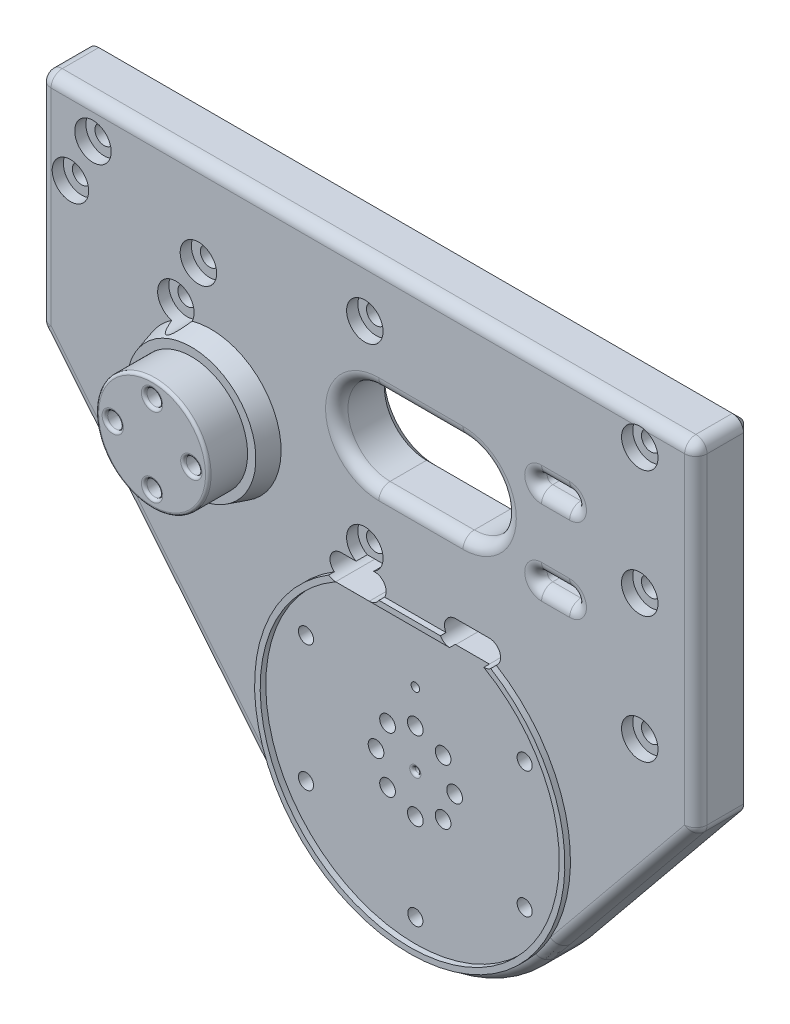
SolidWorks part; units mm, degrees
ref_plane "Front Plane" through (0, 0, 0) normal (0, 0, 1) x (1, 0, 0)
ref_plane "Top Plane" through (0, 0, 0) normal (0, 1, 0) x (1, 0, 0)
ref_plane "Right Plane" through (0, 0, 0) normal (1, 0, 0) x (0, 0, -1)
sketch "Sketch1" plane through (0, 0, 0) normal (0, 0, 1) x (1, 0, 0)
  line L0 (-36.42, 37.54) -> (-36.42, 0) construction
  line L1 (-66.92, 75) -> (50, 75)
  line L2 (-66.92, 75) -> (-66.92, -30)
  line L3 (-66.92, -30) -> (50, -30)
  line L4 (50, 75) -> (50, -30)
  line L5 (-36.42, 0) -> (0, 0) construction
  circle A0 centre (0, 0) radius 0.5
  circle A1 centre (-36.42, 37.54) radius 0.5
  dimension "D1" = 1
  dimension "D2" = 1
  dimension "D3" = 36.42
  dimension "D4" = 37.54
  dimension "D5" = 50
  dimension "D6" = 30
  dimension "D7" = 30
  dimension "D8" = 37.46
extrude "Boss-Extrude1" add sketch "Sketch1" along normal blind 10
ref_axis "Axis1" through (-36.42, 37.54, 10) along (0, 0, -1)
ref_plane "Plane1" through (0, 37.54, 0) normal (0, 1, 0) x (0, 0, -1)
sketch "Sketch5" plane through (0, 37.54, 0) normal (0, 1, 0) x (0, 0, -1)
  line L0 (-10, 36.92) -> (-10, 35.92) construction
  line L1 (-10, 36.92) -> (-10, 35.92) construction
  line L2 (-10, 36.42) -> (-20.5, 36.42) construction
  line L3 (-20.5, 36.42) -> (-20.5, 26.395)
  line L4 (-20.5, 26.395) -> (-13.5, 26.395)
  line L5 (-13.5, 26.395) -> (-13.5, 24.92)
  line L6 (-13.5, 24.92) -> (-10, 23.92)
  line L7 (-10, 66.92) -> (-10, -50) construction
  line L8 (-10, 36.42) -> (-10, 23.92)
  line L9 (-10, 36.42) -> (-20.5, 36.42)
  line L11 (-13.5, 108.28) -> (-13.5, 138.68) construction
  dimension "D1" = 23
  dimension "D2" = 20.05
  dimension "D3" = 7
  dimension "D4" = 12.5
  dimension "D5" = 3.5
revolve "Revolve1" add sketch "Sketch5" angle 360 about L9
sketch "Sketch6" plane through (0, 0, 20.5) normal (0, 0, 1) x (1, 0, 0)
  line L0 (-36.42, 37.54) -> (-36.42, 44.54) construction
  circle A0 centre (-36.42, 44.54) radius 1.4
  circle A1 centre (-29.42, 37.54) radius 1.4
  circle A2 centre (-36.42, 30.54) radius 1.4
  circle A3 centre (-43.42, 37.54) radius 1.4
  point P13 (-36.42, 37.54)
  dimension "D1" = 7
  dimension "D2" = 2.8
  dimension "D3" = 4
extrude "Cut-Extrude1" cut sketch "Sketch6" against normal through all
sketch "Sketch10" plane through (0, 0, 0) normal (0, 0, -1) x (-1, 0, 0)
  circle A0 centre (0, 0) radius 22.5 construction
  circle A1 centre (-19.484, 11.2528) radius 1.35
  arc A7 (-19.4838, 12.2778) -> (-19.4841, 10.2278) centre (-19.484, 11.2528) ccw construction
  arc A8 (-19.4838, 12.2778) -> (-19.4841, 10.2278) centre (-19.484, 11.2528) ccw construction
  arc A9 (19.4873, 12.2722) -> (19.487, 10.2222) centre (19.4872, 11.2472) ccw construction
  arc A10 (19.4841, -10.2278) -> (19.4838, -12.2778) centre (19.484, -11.2528) ccw construction
  arc A11 (-0.0031, -21.475) -> (-0.0033, -23.525) centre (-0.0032, -22.5) ccw construction
  arc A12 (-19.487, -10.2222) -> (-19.4873, -12.2722) centre (-19.4872, -11.2472) ccw construction
  arc A13 (19.4873, 12.2722) -> (19.487, 10.2222) centre (19.4872, 11.2472) ccw construction
  arc A14 (19.4841, -10.2278) -> (19.4838, -12.2778) centre (19.484, -11.2528) ccw construction
  arc A15 (-0.0031, -21.475) -> (-0.0033, -23.525) centre (-0.0032, -22.5) ccw construction
  arc A16 (-19.487, -10.2222) -> (-19.4873, -12.2722) centre (-19.4872, -11.2472) ccw construction
  circle A17 centre (-19.4872, -11.2472) radius 1.35
  circle A18 centre (-0.0032, -22.5) radius 1.35
  circle A19 centre (19.484, -11.2528) radius 1.35
  circle A20 centre (19.4872, 11.2472) radius 1.35
  point P17 (0, 0)
  dimension "D1" = 45
  dimension "D2" = 2.7
extrude "Ak45 holes" cut sketch "Sketch10" against normal through all
fillet "Fillet3" radius 0.5 6 edges at (-46.445, 37.54, 20.5) (-42.02, 37.54, 20.5) (-35.02, 30.54, 20.5) (-28.02, 37.54, 20.5) (-35.02, 44.54, 20.5) (0.5, 0, 10)
hole_wizard "CBORE for M5 Hex Head Bolt1" positions "3DSketch1" profile "Sketch14" counterbore size "M5" standard "ANSI Metric" end condition through all
sketch3d "3DSketch1"
  line L4 (19.484, 11.2528, 10) -> (19.484, 11.2528, 0) construction
  line L5 (19.4872, -11.2472, 10) -> (19.4872, -11.2472, 0) construction
  line L6 (0.0032, -22.5, 10) -> (0.0032, -22.5, 0) construction
  line L7 (-19.484, -11.2528, 10) -> (-19.484, -11.2528, 0) construction
  line L8 (-19.4872, 11.2472, 10) -> (-19.4872, 11.2472, 0) construction
  point P16 (19.484, 11.2528, 0)
  point P30 (19.4872, -11.2472, 0)
  point P34 (0.0032, -22.5, 0)
  point P38 (-19.484, -11.2528, 0)
  point P42 (-19.4872, 11.2472, 0)
sketch "Sketch14" plane through (19.484, 11.2528, 0) normal (1, 0, 0) x (0, 1, 0)
  line L0 (0, 0) -> (0, 20.5)
  line L1 (0, 20.5) -> (1.35, 20.5)
  line L3 (1.35, 20.5) -> (1.35, 2.5)
  line L4 (1.35, 2.5) -> (2.75, 2.5)
  line L5 (2.75, 2.5) -> (2.75, 0)
  line L7 (2.75, 0) -> (0, 0)
  line L11 (0, -6.35) -> (0, 107.95) construction
  dimension "Thru Hole Dia." = 2.7
  dimension "Thru Hole Depth" = 20.5
  dimension "C'Bore Dia." = 5.5
  dimension "C'Bore Depth" = 2.5
sketch "Sketch16" plane through (0, 0, 10) normal (0, 0, 1) x (1, 0, 0)
  line L0 (13.199, 23.1519) -> (-13.2056, 23.1481)
  line L1 (-12.1276, 22.9983) -> (12.1211, 23.0017) construction
  line L3 (13.4613, 24.1519) -> (-13.4682, 24.1481)
  arc A0 (-13.2056, 23.1481) -> (13.199, 23.1519) centre (0, 0) ccw
  arc A2 (0.0038, -26.5) -> (13.1592, 23.0019) centre (0, 0) ccw construction
  arc A3 (0.0038, -26.5) -> (13.1592, 23.0019) centre (0, 0) ccw construction
  arc A4 (-13.4682, 24.1481) -> (13.4613, 24.1519) centre (0, 0) ccw
  dimension "D2" = 26.5
  dimension "D3" = 26.65
  dimension "D1" = 0.15
  dimension "D4" = 1
extrude "Boss-Extrude4" add sketch "Sketch16" along normal blind 1
sketch "Sketch17" plane through (0, 0, 10) normal (0, 0, 1) x (1, 0, 0)
  line L0 (0, 7) -> (0, 0) construction
  circle A0 centre (0, 7) radius 1.4
  circle A1 centre (4.9497, 4.9497) radius 1.4
  circle A2 centre (7, 0) radius 1.4
  circle A3 centre (4.9497, -4.9497) radius 1.4
  circle A4 centre (0, -7) radius 1.4
  circle A5 centre (-4.9497, -4.9497) radius 1.4
  circle A6 centre (-7, 0) radius 1.4
  circle A7 centre (-4.9497, 4.9497) radius 1.4
  point P13 (0, 0)
  dimension "D1" = 2.8
  dimension "D2" = 7
  dimension "D3" = 8
extrude "Cut-Extrude5" cut sketch "Sketch17" against normal through all
sketch "WheelPointTravel" plane through (0, 0, 10) normal (0, 0, 1) x (1, 0, 0)
  line L0 (-67.04, -61.85) -> (-67.04, -341.8) construction
  line L1 (-57.865, -61.85) -> (-76.215, -61.85)
  line L2 (-57.865, -61.85) -> (-57.865, -341.8)
  line L3 (-57.865, -341.8) -> (-76.215, -341.8)
  line L4 (-76.215, -61.85) -> (-76.215, -341.8)
  dimension "D1" = 67.04
  dimension "D2" = 18.35
  dimension "D3" = 61.85
  dimension "D4" = 279.95
sketch "Angle Retracted Extended" plane through (0, 0, 0) normal (0, 0, -1) x (-1, 0, 0)
  line L0 (0, 0) -> (316.0647, 168.0546) construction
  line L1 (138.3785, -213.0843) -> (0, 0) construction
  line L2 (0, 0) -> (228.0086, 0) construction
  dimension "D1" = 28
  dimension "D2" = 57
sketch "Sketch18" plane through (0, 0, 10) normal (0, 0, 1) x (1, 0, 0)
  circle A0 centre (-57.4513, 68.5011) radius 1.6 construction
  circle A1 centre (-38.6577, 59.131) radius 1.6 construction
  circle A2 centre (-42.6735, 51.0766) radius 1.65 construction
  circle A3 centre (-61.4671, 60.4467) radius 1.65 construction
  circle A4 centre (-42.6735, 51.0766) radius 1.65
  circle A5 centre (-61.4671, 60.4467) radius 1.65
  circle A7 centre (-57.4513, 68.5011) radius 1.6
  circle A8 centre (-38.6577, 59.131) radius 1.6
  circle A14 centre (40, 70) radius 1.7 construction
  circle A15 centre (40, 47.5) radius 1.7 construction
  circle A16 centre (40, 25) radius 1.7 construction
  circle A17 centre (-9, 30) radius 1.7 construction
  circle A18 centre (-9, 65) radius 1.7 construction
  circle A19 centre (40, 70) radius 1.7
  circle A20 centre (40, 47.5) radius 1.7
  circle A21 centre (40, 25) radius 1.7
  circle A22 centre (-9, 30) radius 1.7
  circle A23 centre (-9, 65) radius 1.7
extrude "Fastener holes" cut sketch "Sketch18" against normal through all
hole_wizard "CBORE for M5 Hex Head Bolt2" positions "3DSketch2" profile "Sketch19" counterbore size "M5" standard "ANSI Metric" end condition through all
sketch3d "3DSketch2"
  line L0 (-57.4513, 68.5011, 0) -> (-57.4513, 68.5011, 10) construction
  line L6 (-38.6577, 59.131, 0) -> (-38.6577, 59.131, 10) construction
  line L7 (-9, 65, 0) -> (-9, 65, 10) construction
  line L8 (-9, 30, 0) -> (-9, 30, 10) construction
  line L9 (40, 25, 0) -> (40, 25, 10) construction
  line L10 (40, 47.5, 0) -> (40, 47.5, 10) construction
  line L11 (40, 70, 0) -> (40, 70, 10) construction
  line L12 (-61.4671, 60.4467, 0) -> (-61.4671, 60.4467, 10) construction
  line L13 (-61.4671, 60.4467, 0) -> (-61.4671, 60.4467, 10) construction
  line L14 (-42.6735, 51.0766, 0) -> (-42.6735, 51.0766, 10) construction
  point P0 (-57.4513, 68.5011, 10)
  point P29 (-38.6577, 59.131, 10)
  point P36 (-9, 65, 10)
  point P40 (-9, 30, 10)
  point P44 (40, 25, 10)
  point P48 (40, 47.5, 10)
  point P52 (40, 70, 10)
  point P57 (-61.4671, 60.4467, 10)
  point P61 (-61.4671, 60.4467, 10)
  point P65 (-42.6735, 51.0766, 10)
sketch "Sketch19" plane through (-57.4513, 68.5011, 10) normal (1, 0, 0) x (0, -1, 0)
  line L0 (0, 0) -> (0, 10)
  line L1 (0, 10) -> (1.65, 10)
  line L3 (1.65, 10) -> (1.65, 2)
  line L4 (1.65, 2) -> (3.25, 2)
  line L5 (3.25, 2) -> (3.25, 0)
  line L7 (3.25, 0) -> (0, 0)
  line L11 (0, -6.35) -> (0, 107.95) construction
  dimension "Thru Hole Dia." = 3.3
  dimension "Thru Hole Depth" = 10
  dimension "C'Bore Dia." = 6.5
  dimension "C'Bore Depth" = 2
sketch "Sketch20" plane through (0, 0, 0) normal (0, 0, -1) x (-1, 0, 0)
  line L0 (-50, 15) -> (-22.6599, -18.4957)
  line L1 (-50, -30) -> (-50, 75) construction
  line L2 (22.6352, -18.5259) -> (66.92, 35.582)
  line L3 (0, 0) -> (316.0647, 168.0546) construction
  line L4 (66.92, 75) -> (66.92, -30) construction
  line L5 (-50, 15) -> (-50, -30)
  line L6 (-50, -30) -> (66.92, -30)
  line L7 (66.92, -30) -> (66.92, 35.582)
  arc A0 (-22.6599, -18.4957) -> (22.6352, -18.5259) centre (0, 0) ccw
  circle A1 centre (-40, 25) radius 1.7 construction
  dimension "D1" = 58.5
  dimension "D2" = 10
extrude "Cut-Extrude7" cut sketch "Sketch20" against normal through all
sketch "Sketch21" plane through (0, 0, 0) normal (0, 0, -1) x (-1, 0, 0)
  line L0 (6.5, 40.5) -> (-8.5, 40.5) construction
  line L1 (-8.5, 55.5) -> (6.5, 55.5) construction
  line L2 (6.5, 40.5) -> (-8.5, 40.5)
  line L3 (-8.5, 55.5) -> (6.5, 55.5)
  line L4 (-22.5, 39.5) -> (-27.5, 39.5) construction
  line L5 (-27.5, 41.5) -> (-22.5, 41.5) construction
  line L6 (-22.5, 54.5) -> (-27.5, 54.5) construction
  line L7 (-27.5, 56.5) -> (-22.5, 56.5) construction
  line L8 (-22.5, 39.5) -> (-27.5, 39.5)
  line L9 (-27.5, 41.5) -> (-22.5, 41.5)
  line L10 (-22.5, 54.5) -> (-27.5, 54.5)
  line L11 (-27.5, 56.5) -> (-22.5, 56.5)
  arc A0 (6.5, 40.5) -> (6.5, 55.5) centre (6.5, 48) ccw construction
  arc A1 (-8.5, 55.5) -> (-8.5, 40.5) centre (-8.5, 48) ccw construction
  arc A2 (6.5, 40.5) -> (6.5, 55.5) centre (6.5, 48) ccw
  arc A3 (-8.5, 55.5) -> (-8.5, 40.5) centre (-8.5, 48) ccw
  arc A4 (-22.5, 39.5) -> (-22.5, 41.5) centre (-22.5, 40.5) ccw construction
  arc A5 (-27.5, 41.5) -> (-27.5, 39.5) centre (-27.5, 40.5) ccw construction
  arc A6 (-22.5, 54.5) -> (-22.5, 56.5) centre (-22.5, 55.5) ccw construction
  arc A7 (-27.5, 56.5) -> (-27.5, 54.5) centre (-27.5, 55.5) ccw construction
  arc A8 (-22.5, 39.5) -> (-22.5, 41.5) centre (-22.5, 40.5) ccw
  arc A9 (-27.5, 41.5) -> (-27.5, 39.5) centre (-27.5, 40.5) ccw
  arc A10 (-22.5, 54.5) -> (-22.5, 56.5) centre (-22.5, 55.5) ccw
  arc A11 (-27.5, 56.5) -> (-27.5, 54.5) centre (-27.5, 55.5) ccw
extrude "Cable hole" cut sketch "Sketch21" against normal through all
sketch "Sketch22" plane through (0, 0, 10) normal (0, 0, 1) x (1, 0, 0)
  circle A0 centre (-61.4671, 60.4467) radius 3.25 construction
  circle A1 centre (-61.4671, 60.4467) radius 3.25
  circle A2 centre (-42.6735, 51.0766) radius 3.25
extrude "Cut-Extrude9" cut sketch "Sketch22" along normal through all
fillet "Fillet4" radius 2 21 edges at (28.5, 55.5, 10) (25, 54.5, 10) (21.5, 55.5, 10) (28.5, 40.5, 10) (25, 39.5, 10) (21.5, 40.5, 10) (16, 48, 10) (1, 40.5, 10) (-14, 48, 10) (36.33, -1.7478, 10) (25, 56.5, 10) (25, 41.5, 10) (1, 55.5, 10) (50, 15, 5) (-66.92, 35.582, 5) (50, 75, 5) (-66.92, 75, 5) (50, 45, 10) (-44.7776, 8.5281, 10) (-66.92, 55.291, 10) (-8.46, 75, 10)
chamfer "Chamfer1" distance 1.5 angle 45 14 edges at (49.884, 15.0413, 0) (50, 44.3563, 0) (36.1047, -2.0239, 0) (49.4142, 74.4142, 0) (0.0195, -29.25, 0) (-8.46, 75, 0) (-44.5515, 8.2517, 0) (-66.3342, 74.4142, 0) (-66.8035, 35.6236, 0) (-66.92, 54.6481, 0) (1, 40.5, 0) (-14, 48, 0) (16, 48, 0) (1, 55.5, 0)
sketch "Sketch23" plane through (0, 0, 0) normal (0, 0, -1) x (-1, 0, 0)
  circle A0 centre (0, 13) radius 0.75 construction
  circle A1 centre (0, 13) radius 0.75
extrude "Cut-Extrude10" cut sketch "Sketch23" against normal through all
sketch "Sketch24" plane through (0, 0, 10) normal (0, 0, 1) x (1, 0, 0)
  line L0 (13.199, 25.149) -> (7.199, 25.149) construction
  line L1 (13.199, 23.149) -> (7.199, 23.149)
  line L2 (13.199, 27.149) -> (7.199, 27.149)
  line L3 (-13.2056, 25.149) -> (-7.2056, 25.149) construction
  line L4 (-13.2056, 27.149) -> (-7.2056, 27.149)
  line L5 (-13.2056, 23.149) -> (-7.2056, 23.149)
  line L6 (13.199, 23.1519) -> (-13.2056, 23.1481) construction
  arc A0 (13.199, 23.149) -> (13.199, 27.149) centre (13.199, 25.149) ccw
  arc A1 (7.199, 27.149) -> (7.199, 23.149) centre (7.199, 25.149) ccw
  arc A2 (-13.2056, 27.149) -> (-13.2056, 23.149) centre (-13.2056, 25.149) ccw
  arc A3 (-7.2056, 23.149) -> (-7.2056, 27.149) centre (-7.2056, 25.149) ccw
  point P2 (10.199, 25.149)
  point P7 (-10.2056, 25.149)
  point P14 (0, 0)
  point P15 (-7.2056, 23.149)
  dimension "D1" = 6
  dimension "D2" = 4
extrude "Cut-Extrude11" cut sketch "Sketch24" against normal through all and the other way through all
